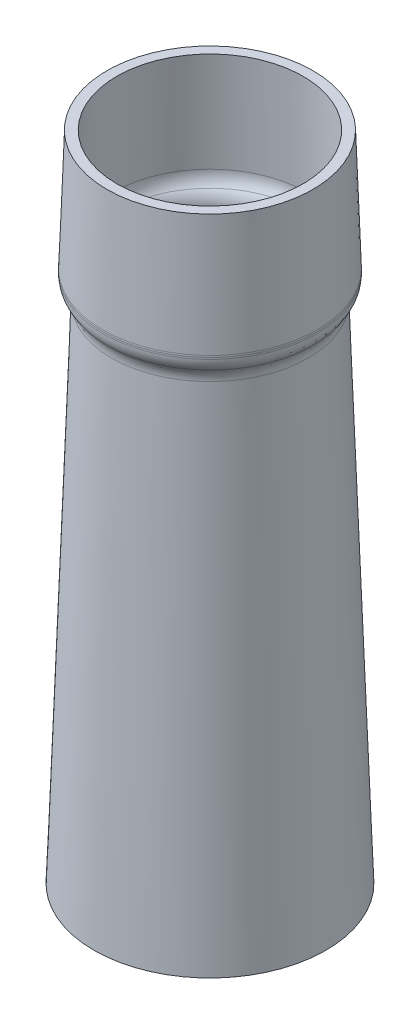
SolidWorks part; units mm, degrees
ref_plane "Front Plane" through (0, 0, 0) normal (0, 0, 1) x (1, 0, 0)
ref_plane "Top Plane" through (0, 0, 0) normal (0, 1, 0) x (1, 0, 0)
ref_plane "Right Plane" through (0, 0, 0) normal (1, 0, 0) x (0, 0, -1)
sketch "Sketch1" plane through (0, 0, 0) normal (0, 1, 0) x (1, 0, 0)
  circle A0 centre (0, 0) radius 4.755
  dimension "D1" = 9.51
extrude "Boss-Extrude1" add sketch "Sketch1" against normal blind 33.3 draft 2 draft outward yes
sketch "Sketch2" plane through (0, 0, 0) normal (0, 1, 0) x (1, 0, 0)
  circle A0 centre (0, 0) radius 4.255
  dimension "D1" = 8.51
extrude "Cut-Extrude1" cut sketch "Sketch2" against normal blind 33.3 draft 2 draft outward yes
sketch "Sketch3" plane through (0, 0, 0) normal (0, 1, 0) x (1, 0, 0)
  circle A0 centre (0, 0) radius 7.293
  dimension "D1" = 14.5859
extrude "Cut-Extrude2" cut sketch "Sketch3" against normal blind 6.2
sketch "Sketch4" plane through (0, -6.2, 0) normal (0, 1, 0) x (1, 0, 0)
  circle A0 centre (0, 0) radius 5.4715
  dimension "D1" = 10.943
extrude "Boss-Extrude2" add sketch "Sketch4" along normal blind 6.2 draft 2
sketch "Sketch5" plane through (0, 0, 0) normal (0, 1, 0) x (1, 0, 0)
  circle A0 centre (0, 0) radius 4.755
  dimension "D1" = 9.51
extrude "Cut-Extrude3" cut sketch "Sketch5" against normal blind 6.2 draft 2 draft outward yes
sketch "Sketch8" plane through (0, -6.2, 0) normal (0, 1, 0) x (1, 0, 0)
  circle A0 centre (0, 0) radius 4.4715
  circle A1 centre (0, 0) radius 5.4715
  dimension "D1" = 8.943
  dimension "D2" = 10.943
extrude "Boss-Extrude3" add sketch "Sketch8" along normal blind 0.1 and the other way blind 0.5
fillet "Fillet3" radius 1 1 edges at (0, -6.7, 4.4715)
fillet "Fillet4" radius 1 1 edges at (0, -6.1, 4.968)
fillet "Fillet5" radius 1 1 edges at (0, -6.1, 4.4715)
fillet "Fillet6" radius 1 1 edges at (0, -6.7, 4.989)
fillet "Fillet7" radius 1 2 edges at (0, -6.7, 5.4715) (0, -6.1, 5.4715)
